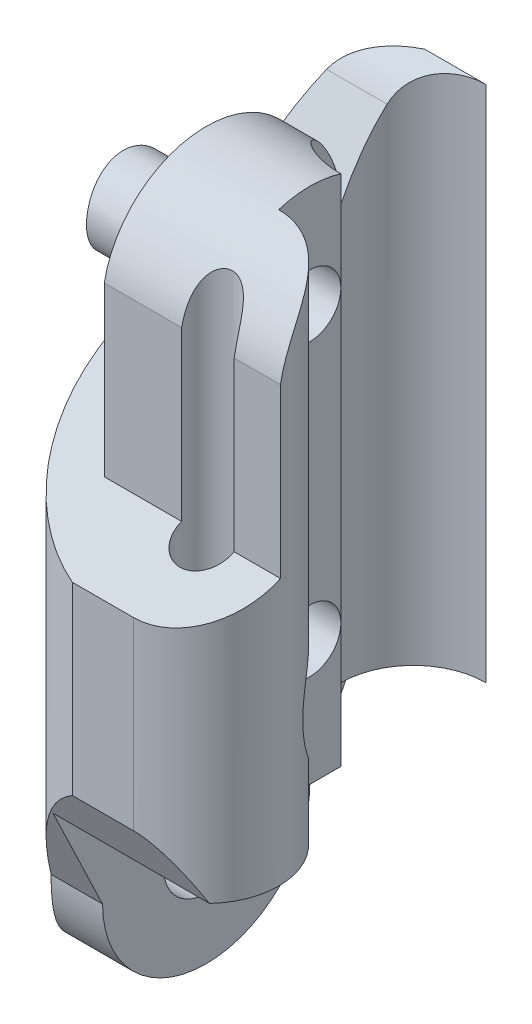
SolidWorks part; units mm, degrees
ref_plane "Front Plane" through (0, 0, 0) normal (0, 0, 1) x (1, 0, 0)
ref_plane "Top Plane" through (0, 0, 0) normal (0, 1, 0) x (1, 0, 0)
ref_plane "Right Plane" through (0, 0, 0) normal (1, 0, 0) x (0, 0, -1)
sketch "Sketch1" plane through (0, 0, 0) normal (0, 1, 0) x (1, 0, 0)
  line L0 (-2.958, 8.5) -> (2.958, 8.5)
  line L1 (-2.958, -8.5) -> (2.958, -8.5)
  arc A0 (-2.958, 8.5) -> (-2.958, -8.5) centre (0, 0) ccw
  arc A1 (2.958, 8.5) -> (2.958, -8.5) centre (0, 0) cw
  point P9 (-9, 0)
  point P10 (9, 0)
  dimension "D1" = 18
  dimension "D2" = 17
extrude "Boss-Extrude1" add sketch "Sketch1" along normal blind 35
sketch "Sketch2" plane through (0, 0, 0) normal (0, -1, 0) x (1, 0, 0)
  circle A0 centre (0, -5) radius 1.27
  circle A1 centre (0, 5) radius 1.27
  dimension "D1" = 2.54
  dimension "D2" = 5
  dimension "D3" = 5
extrude "Cut-Extrude1" cut sketch "Sketch2" against normal blind 35
sketch "Sketch3" plane through (0, 0, -8.5) normal (0, 0, -1) x (-1, 0, 0)
  line L0 (5, 0) -> (5, 10)
  line L1 (5, 10) -> (-5, 10)
  line L2 (-5, 10) -> (-5, 0)
  line L3 (5, 0) -> (-5, 0)
  line L4 (-2.958, 0) -> (2.958, 0) construction
  point P10 (0, 0)
  dimension "D1" = 10
  dimension "D2" = 10
extrude "Cut-Extrude2" cut sketch "Sketch3" against normal up to surface (17 mm away) up to face at (0, 17.5, 8.5)
sketch "Sketch4" plane through (5, 0, 0) normal (-1, 0, 0) x (0, 0, 1)
  line L0 (-7.4833, 10) -> (-5, 5)
  line L1 (8.5, 12.3086) -> (5, 5)
  line L2 (7.4833, 0) -> (-7.4833, 0) construction
  line L3 (-7.4833, 10) -> (-9.8579, -1.8222)
  line L4 (-9.8579, -1.8222) -> (9.8579, -1.8222)
  line L6 (8.5, 35) -> (8.5, 10) construction
  line L7 (9.8579, -1.8222) -> (8.5, 12.3086)
  arc A0 (-5, 5) -> (5, 5) centre (0, 5) ccw
  circle A1 centre (0, 5) radius 2.05
  point P7 (0, 0)
  dimension "D1" = 4.1
  dimension "D2" = 5
  dimension "D3" = 12.0584
  dimension "D4" = 37.769
extrude "Cut-Extrude3" cut sketch "Sketch4" against normal mid plane 35
ref_plane "Plane1" through (-2.958, 0, 0) normal (-1, 0, 0) x (0, 0, 1)
sketch "Sketch6" plane through (-2.958, 0, 0) normal (-1, 0, 0) x (0, 0, 1)
  line L0 (8.5, 21.2199) -> (0, 25)
  line L1 (8.5, 35) -> (8.5, 12.3086) construction
  line L2 (-5, 30) -> (-6.7559, 33.5353)
  line L3 (8.5, 35) -> (-8.5, 35) construction
  line L4 (8.5, 21.2199) -> (17.803, 42.886)
  line L6 (-7.4833, 10) -> (-5, 5) construction
  line L7 (-8.5, 35) -> (17.803, 42.886)
  arc A0 (0, 25) -> (-5, 30) centre (0, 30) cw
  circle A1 centre (0, 30) radius 2
  arc A2 (-6.7559, 33.5353) -> (-8.5, 35) centre (-9.3069, 32.2683) ccw
  dimension "D1" = 5
  dimension "D3" = 4
  dimension "D2" = 5
  dimension "D4" = 8.5
extrude "Cut-Extrude5" cut sketch "Sketch6" against normal blind 9.6 from surface starting at face at (5, 7.05, 0)
sketch "Sketch7" plane through (5, 0, 0) normal (1, 0, 0) x (0, 0, -1)
  line L0 (5, 30) -> (6.7559, 33.5353)
  line L2 (-8.3419, 47.5367) -> (-13.1682, 33.5285)
  line L3 (-7.4833, 35) -> (7.4833, 35) construction
  line L4 (-4.9155, 30.9155) -> (-4.9155, 22.814)
  line L5 (-7.4833, 21.6721) -> (0, 25) construction
  line L6 (-4.9155, 22.814) -> (-10.0468, 20.532)
  line L7 (-10.0468, 20.532) -> (-13.1682, 33.5285)
  line L8 (6.7559, 33.5353) -> (5, 30) construction
  line L9 (8.5, 35) -> (-8.3419, 47.5367)
  arc A0 (5, 30) -> (-4.9155, 30.9155) centre (0, 30) ccw
  arc A1 (6.7559, 33.5353) -> (8.5, 35) centre (9.3069, 32.2683) cw
  arc A2 (7.4833, 34.4564) -> (6.7559, 33.5353) centre (9.3069, 32.2683) ccw construction
  dimension "D1" = 5
fillet "Fillet3" radius 1 2 edges at (0, 10, -3.73) (0, 10, 6.27)
extrude "Cut-Extrude6" cut sketch "Sketch6<3>" along normal blind 6.604 from surface starting at face at (-5, 2.95, 0)
sketch "Sketch6<3>" plane through (-2.958, 0, 0) normal (-1, 0, 0) x (0, 0, 1) same geometry as "Sketch6"
extrude "Cut-Extrude7" cut sketch "Sketch7" against normal blind 14.986
sketch "Sketch8" plane through (0, 10, 0) normal (0, -1, 0) x (1, 0, 0)
  line L0 (0, 1.5) -> (0, -1.5)
  line L1 (-2.958, -8.5) -> (2.958, -8.5) construction
  line L2 (2.958, 8.5) -> (-2.958, 8.5) construction
  line L3 (0, 8.5) -> (-4.7901, 15.219)
  line L4 (-4.7901, 15.219) -> (34.9648, -1.5)
  line L5 (34.9648, -1.5) -> (-4.7901, -16.0136)
  line L6 (-4.7901, -16.0136) -> (0, -8.5)
  arc A0 (0, -1.5) -> (0, -8.5) centre (0, -5) ccw
  arc A1 (0, 1.5) -> (0, 8.5) centre (0, 5) ccw
  circle A2 centre (0, 5) radius 2.27 construction
  circle A3 centre (0, -5) radius 2.27 construction
extrude "Cut-Extrude8" cut sketch "Sketch8" against normal mid plane 62.992
sketch "Sketch9" plane through (0, 0, 0) normal (1, 0, 0) x (0, 0, -1)
  line L1 (1.5, 10) -> (-1.5, 10) construction
  circle A0 centre (0, 16) radius 1.5
  dimension "D2" = 3
  dimension "D1" = 6
extrude "Cut-Extrude9" cut sketch "Sketch9" against normal blind 14.224
sketch "Sketch13" plane through (0, 0, 0) normal (1, 0, 0) x (0, 0, -1)
  line L1 (1.5, 34.7697) -> (1.5, 16) construction
  circle A0 centre (0, 30) radius 1.5
  circle A2 centre (0, 30) radius 2 construction
sketch "Sketch14" plane through (0, 0, 0) normal (1, 0, 0) x (0, 0, -1)
  line L0 (0, 12.5) -> (0, 19.5)
  arc A0 (0, 19.5) -> (0, 12.5) centre (0, 16) ccw
  arc A1 (-1.5, 16) -> (1.5, 16) centre (0, 16) ccw construction
  dimension "D1" = 3.5
extrude "Cut-Extrude11" cut sketch "Sketch14" along normal blind 6.048
extrude "Cut-Extrude12" cut sketch "Sketch13" against normal blind 3
sketch "Sketch15" plane through (0, 0, 0) normal (1, 0, 0) x (0, 0, -1)
  circle A0 centre (0, 16) radius 2.75
  dimension "D1" = 5.5
extrude "Cut-Extrude13" cut sketch "Sketch15" against normal blind 7.572 from offset 5.5 offset against normal yes
